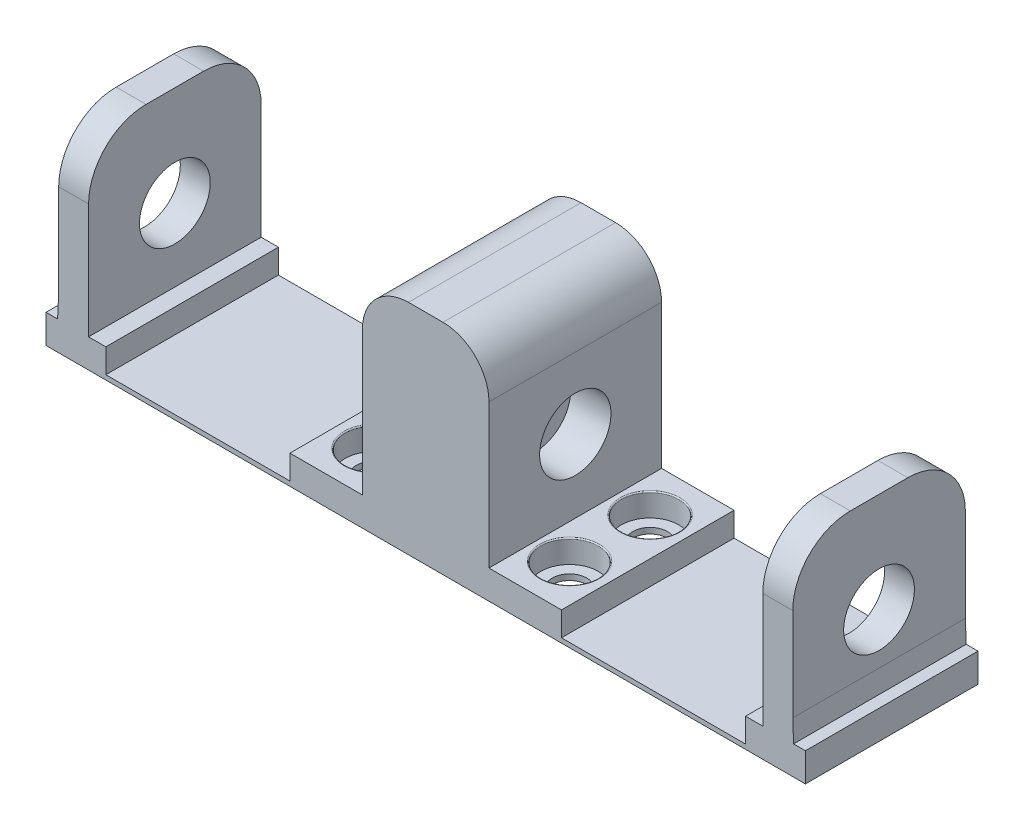
SolidWorks part; units mm, degrees
ref_plane "Alzado" through (0, 0, 0) normal (0, 0, 1) x (1, 0, 0)
ref_plane "Planta" through (0, 0, 0) normal (0, 1, 0) x (1, 0, 0)
ref_plane "Vista lateral" through (0, 0, 0) normal (1, 0, 0) x (0, 0, -1)
sketch "Croquis1" plane through (0, 0, 0) normal (0, 0, 1) x (1, 0, 0)
  line L0 (0, 9.5) -> (0, -9.5) construction
  line L1 (-1.5, 9.5) -> (1.5, 9.5)
  line L2 (-5.5, 5.5) -> (-5.5, -7)
  line L3 (-5.5, -9.5) -> (5.5, -9.5)
  line L4 (5.5, 5.5) -> (5.5, -7)
  line L5 (-5.5, 9.5) -> (5.5, -9.5) construction
  line L6 (-5.5, -9.5) -> (5.5, 9.5) construction
  line L7 (-5.5, -9.5) -> (-11.5, -9.5)
  line L9 (-5.5, -7) -> (-11.5, -7)
  line L10 (-11.5, -9.5) -> (-11.5, -7)
  line L11 (5.5, -7) -> (11.5, -7)
  line L12 (11.5, -9.5) -> (11.5, -7)
  line L13 (5.5, -9.5) -> (11.5, -9.5)
  arc A0 (5.5, 5.5) -> (1.5, 9.5) centre (1.5, 5.5) ccw
  arc A1 (-5.5, 5.5) -> (-1.5, 9.5) centre (-1.5, 5.5) cw
  point P0 (0, 0)
  dimension "D1" = 4
  dimension "D2" = 6
  dimension "D3" = 2.5
  dimension "D4" = 11
  dimension "D5" = 15
extrude "Saliente-Extruir1" add sketch "Croquis1" against normal blind 15
sketch "Croquis2" plane through (5.5, 0, 0) normal (1, 0, 0) x (0, 0, -1)
  line L0 (7.5, 9.5) -> (7.5, -7) construction
  line L1 (15, 9.5) -> (0, 9.5) construction
  line L2 (15, -7) -> (0, -7) construction
  line L3 (15, -9.5) -> (0, -9.5) construction
  circle A0 centre (7.5, -0.68) radius 3.1
  dimension "D2" = 6.2
  dimension "D1" = 8.82
extrude "Cortar-Extruir1" cut sketch "Croquis2" against normal blind 3.5
sketch "Croquis3" plane through (-5.5, 0, 0) normal (-1, 0, 0) x (0, 0, 1)
  line L0 (-7.5, 9.5) -> (-7.5, -7) construction
  line L1 (-15, 9.5) -> (0, 9.5) construction
  line L2 (-15, -7) -> (0, -7) construction
  line L3 (-15, -9.5) -> (0, -9.5) construction
  circle A0 centre (-7.5, -0.68) radius 3.1
  dimension "D2" = 6.2
  dimension "D1" = 8.82
extrude "Cortar-Extruir2" cut sketch "Croquis3" against normal blind 3.5
sketch "Croquis4" plane through (0, -7, 0) normal (0, 1, 0) x (1, 0, 0)
  line L0 (0, 15) -> (0, 0) construction
  line L1 (1.5, 15) -> (-1.5, 15) construction
  line L2 (-8.5, 15) -> (-8.5, 0) construction
  line L3 (-5.5, 15) -> (-11.5, 15) construction
  line L4 (-5.5, 0) -> (-11.5, 0) construction
  circle A0 centre (-8.5, 11) radius 2.5
  circle A1 centre (-8.5, 4) radius 2.5
  circle A2 centre (8.5, 4) radius 2.5
  circle A3 centre (8.5, 11) radius 2.5
  dimension "D1" = 5
  dimension "D2" = 4
  dimension "D3" = 4
extrude "Cortar-Extruir3" cut sketch "Croquis4" against normal blind 2
fillet "Redondeo1" radius 0.1 4 edges at (11, -7, -4) (11, -7, -11) (-11, -7, -4) (-11, -7, -11)
sketch "Croquis5" plane through (0, -7, 0) normal (0, 1, 0) x (1, 0, 0)
  line L0 (-8.5, 15) -> (-8.5, 0) construction
  line L1 (-5.5, 15) -> (-11.5, 15) construction
  line L2 (-5.5, 0) -> (-11.5, 0) construction
  line L3 (0, 15) -> (0, 0) construction
  line L4 (1.5, 15) -> (-1.5, 15) construction
  line L5 (1.5, 0) -> (-1.5, 0) construction
  circle A0 centre (-8.5, 11) radius 1.5
  circle A1 centre (-8.5, 4) radius 1.5
  circle A2 centre (-8.5, 11) radius 2.6 construction
  circle A3 centre (8.5, 4) radius 1.5
  circle A4 centre (8.5, 11) radius 1.5
  dimension "D1" = 3
extrude "Cortar-Extruir4" cut sketch "Croquis5" against normal through all
sketch "Croquis6" plane through (-11.5, 0, 0) normal (-1, 0, 0) x (0, 0, 1)
  line L1 (-15, -7) -> (0, -7)
  line L2 (-15, -7) -> (-15, -9.5)
  line L3 (-15, -9.5) -> (0, -9.5)
  line L4 (0, -7) -> (0, -9.5)
extrude "Saliente-Extruir2" add sketch "Croquis6" along normal blind 21.5
sketch "Croquis7" plane through (11.5, 0, 0) normal (1, 0, 0) x (0, 0, -1)
  line L1 (0, -7) -> (15, -7)
  line L2 (0, -7) -> (0, -9.5)
  line L3 (0, -9.5) -> (15, -9.5)
  line L4 (15, -7) -> (15, -9.5)
extrude "Saliente-Extruir3" add sketch "Croquis7" along normal blind 21.5
sketch "Croquis8" plane through (0, -7, 0) normal (0, 1, 0) x (1, 0, 0)
  line L0 (-5.5, 15) -> (-33, 15) construction
  line L1 (-31.9, 15) -> (-29.3, 15)
  line L2 (-31.9, 15) -> (-31.9, 0)
  line L3 (-31.9, 0) -> (-29.3, 0)
  line L4 (-29.3, 15) -> (-29.3, 0)
  line L5 (-5.5, 0) -> (-33, 0) construction
  line L6 (0, 15) -> (0, 0) construction
  line L7 (1.5, 15) -> (-1.5, 15) construction
  line L8 (31.9, 0) -> (29.3, 0)
  line L9 (29.3, 15) -> (29.3, 0)
  line L10 (31.9, 15) -> (29.3, 15)
  line L11 (31.9, 15) -> (31.9, 0)
  line L12 (-33, 0) -> (-33, 15) construction
  dimension "D1" = 2.6
  dimension "D2" = 1.1
extrude "Saliente-Extruir4" add sketch "Croquis8" along normal blind 15
fillet "Redondeo4" radius 5 2 edges at (-30.6, 8, -15) (-30.6, 8, 0)
fillet "Redondeo5" radius 5 2 edges at (30.6, 8, -15) (30.6, 8, 0)
ref_plane "Plano12" through (0, 0, -7.5) normal (0, 0, 1) x (1, 0, 0)
sketch "Croquis17" plane through (0, 0, -7.5) normal (0, 0, 1) x (1, 0, 0)
  line L0 (31.9, -5.0818) -> (31.9724, -7)
  line L1 (31.9, 3) -> (31.9, -7) construction
  line L3 (33, -7) -> (31.9, -7) construction
rib "Nervio1" sketch "Croquis17" sketch "Croquis17" thickness 15 extrusion direction parallel to sketch draft on no parameters "D1"=15
sketch "Croquis22" plane through (0, 0, -7.5) normal (0, 0, 1) x (1, 0, 0)
  line L0 (-31.9933, -7) -> (-31.9, -5.0818)
  line L1 (-31.9, -7) -> (-33, -7) construction
  line L2 (-31.9, 8) -> (-31.9, 3) construction
  line L4 (-31.9, 3) -> (-31.9, -7) construction
rib "Nervio2" sketch "Croquis22" sketch "Croquis22" thickness 15 extrusion direction parallel to sketch draft on no parameters "D1"=15
sketch "Croquis23" plane through (31.9, 0, 0) normal (1, 0, 0) x (0, 0, -1)
  line L0 (7.5, 8) -> (7.5, -5.0818) construction
  line L1 (5, 8) -> (10, 8) construction
  line L2 (0, -5.0818) -> (15, -5.0818) construction
  line L3 (0, -9.5) -> (15, -9.5) construction
  circle A0 centre (7.5, -0.68) radius 3.075
  dimension "D1" = 6.15
  dimension "D2" = 8.82
extrude "Cortar-Extruir5" cut sketch "Croquis23" against normal blind 7
sketch "Croquis24" plane through (-31.9, 0, 0) normal (-1, 0, 0) x (0, 0, 1)
  line L0 (-7.5, 8) -> (-7.5, -5.0818) construction
  line L1 (-10, 8) -> (-5, 8) construction
  line L2 (-15, -5.0818) -> (0, -5.0818) construction
  line L3 (-15, -9.5) -> (0, -9.5) construction
  circle A0 centre (-7.5, -0.68) radius 3.075
  dimension "D1" = 6.15
  dimension "D2" = 8.82
extrude "Cortar-Extruir6" cut sketch "Croquis24" against normal blind 7
sketch "Croquis34" plane through (0, 0, 0) normal (0, 0, 1) x (1, 0, 0)
  line L0 (-29.3, -7) -> (-27.8, -7)
  line L1 (-5.5, -7) -> (-29.3, -7) construction
  line L2 (-27.8, -7) -> (-27.8, -9.1)
  line L3 (-27.8, -9.1) -> (-11.8, -9.1)
  line L4 (-11.8, -9.1) -> (-11.8, -7)
  line L5 (-27.8, -7) -> (-11.8, -7)
  line L6 (0, -9.5) -> (0, 0) construction
  line L8 (27.8, -7) -> (27.8, -9.1)
  line L9 (27.8, -9.1) -> (11.8, -9.1)
  line L10 (11.8, -9.1) -> (11.8, -7)
  line L11 (27.8, -7) -> (11.8, -7)
  line M23 (-5.5, -7) -> (-29.3, -7)
  dimension "D1" = 16
  dimension "D2" = 1.5
  dimension "D3" = 2.1
extrude "Cortar-Extruir7" cut sketch "Croquis34" against normal through all contours L3 L4 L2 M23 | L11 L10 L9 L8 region at (-19.8, -8.05, 0)
sketch "Croquis35" plane through (0, -9.5, 0) normal (0, -1, 0) x (1, 0, 0)
  line L0 (-31, 0) -> (-31, -15) construction
  line L1 (-33, 0) -> (33, 0) construction
  line L2 (-33, -15) -> (33, -15) construction
  line L3 (-33, -15) -> (-33, 0) construction
  line L4 (0, 0) -> (0, -15) construction
  circle A0 centre (-31, -4) radius 1.5
  circle A1 centre (-31, -11) radius 1.5
  circle A2 centre (31, -11) radius 1.5
  circle A3 centre (31, -4) radius 1.5
  dimension "D2" = 3
  dimension "D3" = 4
  dimension "D1" = 2
  dimension "D4" = 4
extrude "Cortar-Extruir8" cut sketch "Croquis35" against normal blind 2.2
